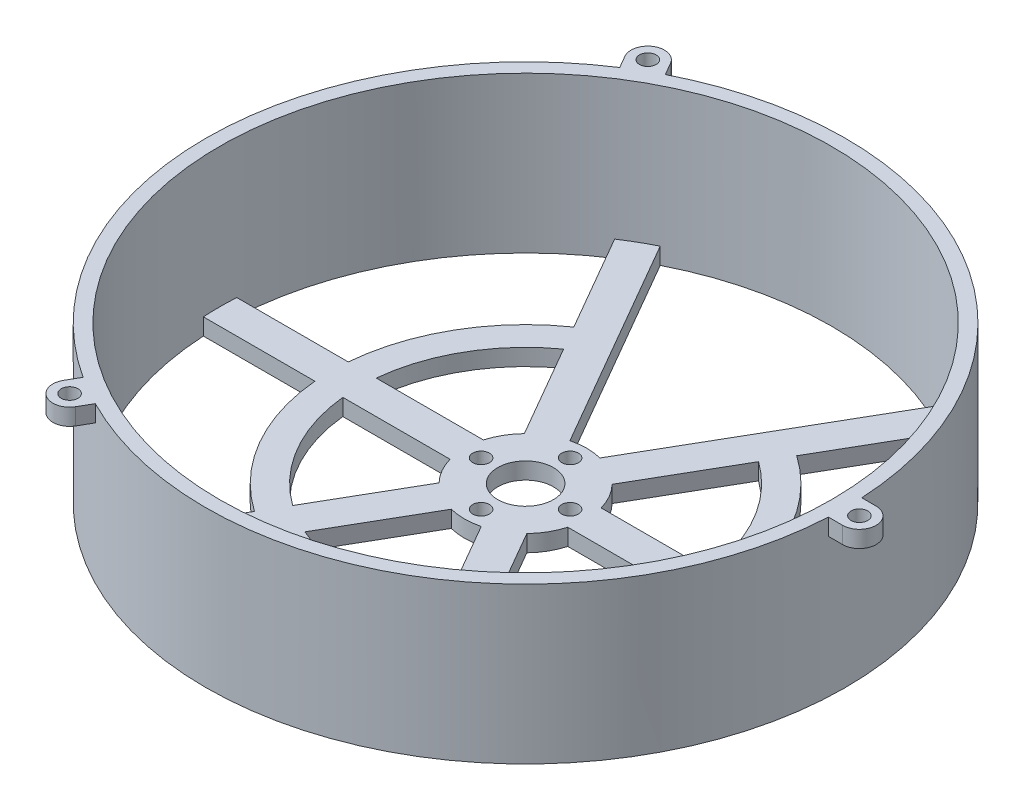
SolidWorks part; units mm, degrees
ref_plane "前视基准面" through (0, 0, 0) normal (0, 0, 1) x (1, 0, 0)
ref_plane "上视基准面" through (0, 0, 0) normal (0, 1, 0) x (1, 0, 0)
ref_plane "右视基准面" through (0, 0, 0) normal (1, 0, 0) x (0, 0, -1)
sketch "草图1" plane through (0, 0, 0) normal (0, 1, 0) x (1, 0, 0)
  line L0 (0, 0) -> (11, 0) construction
  line L1 (10.583, 3) -> (29.8496, 3)
  line L2 (10.583, -3) -> (29.8496, -3)
  line L3 (57.4217, 3) -> (60, 3)
  line L4 (58.5, 0) -> (60, 0) construction
  line L5 (57.4217, -3) -> (60, -3)
  line L6 (7.8896, -7.6652) -> (17.5229, -24.3505)
  line L7 (2.6934, -10.6652) -> (12.3267, -27.3505)
  line L8 (-14.8375, 31.6993) -> (-24.861, 49.0605)
  line L9 (14.8375, 31.6993) -> (24.861, 49.0605)
  line L10 (-2.6934, -10.6652) -> (-12.3267, -27.3505)
  line L11 (-7.8896, -7.6652) -> (-17.5229, -24.3505)
  line L12 (-31.3089, -48.2286) -> (-32.5981, -50.4615)
  line L13 (-26.1128, -51.2286) -> (-27.4019, -53.4615)
  line L14 (-10.583, -3) -> (-29.8496, -3)
  line L15 (-10.583, 3) -> (-29.8496, 3)
  line L16 (20.0337, 28.6993) -> (30.0571, 46.0605)
  line L17 (-20.0337, 28.6993) -> (-30.0571, 46.0605)
  line L18 (-7.8896, 7.6652) -> (-17.5229, 24.3505)
  line L19 (-2.6934, 10.6652) -> (-12.3267, 27.3505)
  line L20 (-26.1128, 51.2286) -> (-27.4019, 53.4615)
  line L21 (-31.3089, 48.2286) -> (-32.5981, 50.4615)
  line L22 (2.6934, 10.6652) -> (12.3267, 27.3505)
  line L23 (7.8896, 7.6652) -> (17.5229, 24.3505)
  line L24 (-34.8712, 3) -> (-54.9181, 3)
  line L25 (-34.8712, -3) -> (-54.9181, -3)
  line L26 (31.3089, 48.2286) -> (32.5981, 50.4615) [skipped]
  line L27 (26.1128, 51.2286) -> (27.4019, 53.4615) [skipped]
  line L28 (-57.4217, 3) -> (-60, 3) [skipped]
  line L29 (-57.4217, -3) -> (-60, -3) [skipped]
  line L30 (26.1128, -51.2286) -> (27.4019, -53.4615) [skipped]
  line L31 (31.3089, -48.2286) -> (32.5981, -50.4615) [skipped]
  line L32 (-20.0337, -28.6993) -> (-30.0571, -46.0605)
  line L33 (34.8712, 3) -> (54.9181, 3)
  line L34 (34.8712, -3) -> (54.9181, -3)
  line L35 (20.0337, -28.6993) -> (30.0571, -46.0605)
  line L36 (14.8375, -31.6993) -> (24.861, -49.0605)
  line L37 (-14.8375, -31.6993) -> (-24.861, -49.0605)
  circle A0 centre (0, 8) radius 1.5
  circle A1 centre (8, 0) radius 1.5
  circle A2 centre (0, -8) radius 1.5
  circle A3 centre (-8, 0) radius 1.5
  circle A4 centre (0, 0) radius 5
  arc A5 (10.583, 3) -> (7.8896, 7.6652) centre (0, 0) ccw
  arc A6 (54.9181, 3) -> (30.0571, 46.0605) centre (0, 0) ccw
  arc A7 (57.4217, 3) -> (-26.1128, 51.2286) centre (0, 0) ccw
  arc A8 (29.8496, 3) -> (17.5229, 24.3505) centre (0, 0) ccw
  arc A9 (34.8712, 3) -> (20.0337, 28.6993) centre (0, 0) ccw
  arc A11 (60, -3) -> (60, 3) centre (60, 0) ccw
  circle A12 centre (60, 0) radius 1.5
  arc A14 (-24.861, -49.0605) -> (24.861, -49.0605) centre (0, 0) ccw
  circle A15 centre (-30, -51.9615) radius 1.5
  arc A16 (-32.5981, -50.4615) -> (-27.4019, -53.4615) centre (-30, -51.9615) ccw
  arc A18 (-26.1128, -51.2286) -> (57.4217, -3) centre (0, 0) ccw
  circle A19 centre (-30, 51.9615) radius 1.5
  arc A20 (-27.4019, 53.4615) -> (-32.5981, 50.4615) centre (-30, 51.9615) ccw
  arc A22 (30.0571, -46.0605) -> (54.9181, -3) centre (0, 0) ccw
  circle A23 centre (30, 51.9615) radius 1.5 [skipped]
  arc A24 (32.5981, 50.4615) -> (27.4019, 53.4615) centre (30, 51.9615) ccw [skipped]
  circle A25 centre (-60, 0) radius 1.5 [skipped]
  arc A26 (-60, 3) -> (-60, -3) centre (-60, 0) ccw [skipped]
  circle A27 centre (30, -51.9615) radius 1.5 [skipped]
  arc A28 (27.4019, -53.4615) -> (32.5981, -50.4615) centre (30, -51.9615) ccw [skipped]
  arc A29 (20.0337, -28.6993) -> (34.8712, -3) centre (0, 0) ccw
  arc A30 (17.5229, -24.3505) -> (29.8496, -3) centre (0, 0) ccw
  arc A31 (7.8896, -7.6652) -> (10.583, -3) centre (0, 0) ccw
  arc A32 (-2.6934, -10.6652) -> (2.6934, -10.6652) centre (0, 0) ccw
  arc A33 (-12.3267, -27.3505) -> (12.3267, -27.3505) centre (0, 0) ccw
  arc A34 (-14.8375, -31.6993) -> (14.8375, -31.6993) centre (0, 0) ccw
  arc A35 (-54.9181, -3) -> (-30.0571, -46.0605) centre (0, 0) ccw
  arc A36 (-34.8712, -3) -> (-20.0337, -28.6993) centre (0, 0) ccw
  arc A37 (-29.8496, -3) -> (-17.5229, -24.3505) centre (0, 0) ccw
  arc A38 (-10.583, -3) -> (-7.8896, -7.6652) centre (0, 0) ccw
  arc A39 (-7.8896, 7.6652) -> (-10.583, 3) centre (0, 0) ccw
  arc A40 (-17.5229, 24.3505) -> (-29.8496, 3) centre (0, 0) ccw
  arc A41 (-20.0337, 28.6993) -> (-34.8712, 3) centre (0, 0) ccw
  arc A42 (-30.0571, 46.0605) -> (-54.9181, 3) centre (0, 0) ccw
  arc A43 (-31.3089, 48.2286) -> (-31.3089, -48.2286) centre (0, 0) ccw
  arc A44 (2.6934, 10.6652) -> (-2.6934, 10.6652) centre (0, 0) ccw
  arc A45 (12.3267, 27.3505) -> (-12.3267, 27.3505) centre (0, 0) ccw
  arc A46 (14.8375, 31.6993) -> (-14.8375, 31.6993) centre (0, 0) ccw
  arc A47 (24.861, 49.0605) -> (-24.861, 49.0605) centre (0, 0) ccw
  point P12 (0, 0)
  point P17 (30, 0)
  point P87 (0, 0)
  dimension "D1" = 3
  dimension "D2" = 8
  dimension "D4" = 10
  dimension "D5" = 22
  dimension "D6" = 110
  dimension "D7" = 115
  dimension "D8" = 60
  dimension "D9" = 5
  dimension "D11" = 3
  dimension "D12" = 3
  dimension "D10" = 60
  dimension "D3" = 4
  dimension "D13" = 6
extrude "凸台-拉伸1" add sketch "草图1" along normal blind 3
sketch "草图2" plane through (0, 3, 0) normal (0, 1, 0) x (1, 0, 0)
  circle A0 centre (0, 0) radius 55
  circle A1 centre (0, 0) radius 57.5
extrude "凸台-拉伸2" add sketch "草图2" along normal blind 25
sketch "草图3" plane through (0, 28, 0) normal (0, 1, 0) x (1, 0, 0)
  line L2 (-32.5981, 50.4615) -> (-31.3089, 48.2286)
  line L3 (-26.1128, 51.2286) -> (-27.4019, 53.4615)
  line L4 (-32.5981, 50.4615) -> (-31.3089, 48.2286)
  line L5 (-26.1128, 51.2286) -> (-27.4019, 53.4615)
  line L6 (60, 3) -> (57.4217, 3)
  line L7 (57.4217, -3) -> (60, -3)
  line L8 (60, 3) -> (57.4217, 3)
  line L9 (57.4217, -3) -> (60, -3)
  line L10 (-27.4019, -53.4615) -> (-26.1128, -51.2286)
  line L11 (-31.3089, -48.2286) -> (-32.5981, -50.4615)
  line L12 (-27.4019, -53.4615) -> (-26.1128, -51.2286)
  line L13 (-31.3089, -48.2286) -> (-32.5981, -50.4615)
  circle A0 centre (60, 0) radius 1.5 construction
  circle A1 centre (-30, 51.9615) radius 1.5 construction
  arc A2 (-26.1128, 51.2286) -> (-31.3089, 48.2286) centre (0, 0) ccw
  arc A3 (-27.4019, 53.4615) -> (-32.5981, 50.4615) centre (-30, 51.9615) ccw
  arc A4 (-26.1128, 51.2286) -> (-31.3089, 48.2286) centre (0, 0) ccw
  arc A5 (-27.4019, 53.4615) -> (-32.5981, 50.4615) centre (-30, 51.9615) ccw
  arc A6 (57.4217, -3) -> (57.4217, 3) centre (0, 0) ccw
  arc A7 (60, -3) -> (60, 3) centre (60, 0) ccw
  arc A8 (57.4217, -3) -> (57.4217, 3) centre (0, 0) ccw
  arc A9 (60, -3) -> (60, 3) centre (60, 0) ccw
  arc A10 (-31.3089, -48.2286) -> (-26.1128, -51.2286) centre (0, 0) ccw
  arc A11 (-32.5981, -50.4615) -> (-27.4019, -53.4615) centre (-30, -51.9615) ccw
  arc A12 (-31.3089, -48.2286) -> (-26.1128, -51.2286) centre (0, 0) ccw
  arc A13 (-32.5981, -50.4615) -> (-27.4019, -53.4615) centre (-30, -51.9615) ccw
  circle A14 centre (-30, -51.9615) radius 1.5 construction
  circle A15 centre (60, 0) radius 1.5
  circle A16 centre (-30, 51.9615) radius 1.5
  circle A17 centre (-30, -51.9615) radius 1.5
  dimension "D1" = 0
  dimension "D2" = 0
  dimension "D3" = 0
extrude "凸台-拉伸3" add sketch "草图3" against normal blind 3
sketch "草图4" plane through (0, 3, 0) normal (0, 1, 0) x (1, 0, 0)
  circle A0 centre (0, 0) radius 57.5
  circle A1 centre (0, 0) radius 69.4751
extrude "切除-拉伸1" cut sketch "草图4" against normal blind 30
sketch "草图5" plane through (0, 0, 0) normal (0, -1, 0) x (1, 0, 0)
  line L0 (-20.0315, -40.6956) -> (-10.068, -23.4382)
  line L1 (-24.861, -49.0605) -> (-14.8375, -31.6993) construction
  line L2 (-12.3267, -27.3505) -> (-2.6934, -10.6652) construction
  line L3 (-10.068, -23.4382) -> (9.2248, -21.9779)
  line L4 (2.6934, -10.6652) -> (12.3267, -27.3505) construction
  line L5 (9.2248, -21.9779) -> (20.0315, -40.6956)
  line L6 (14.8375, -31.6993) -> (24.861, -49.0605) construction
  line L7 (20.0315, -40.6956) -> (-20.0315, -40.6956)
extrude "切除-拉伸2" cut sketch "草图5" against normal blind 10
